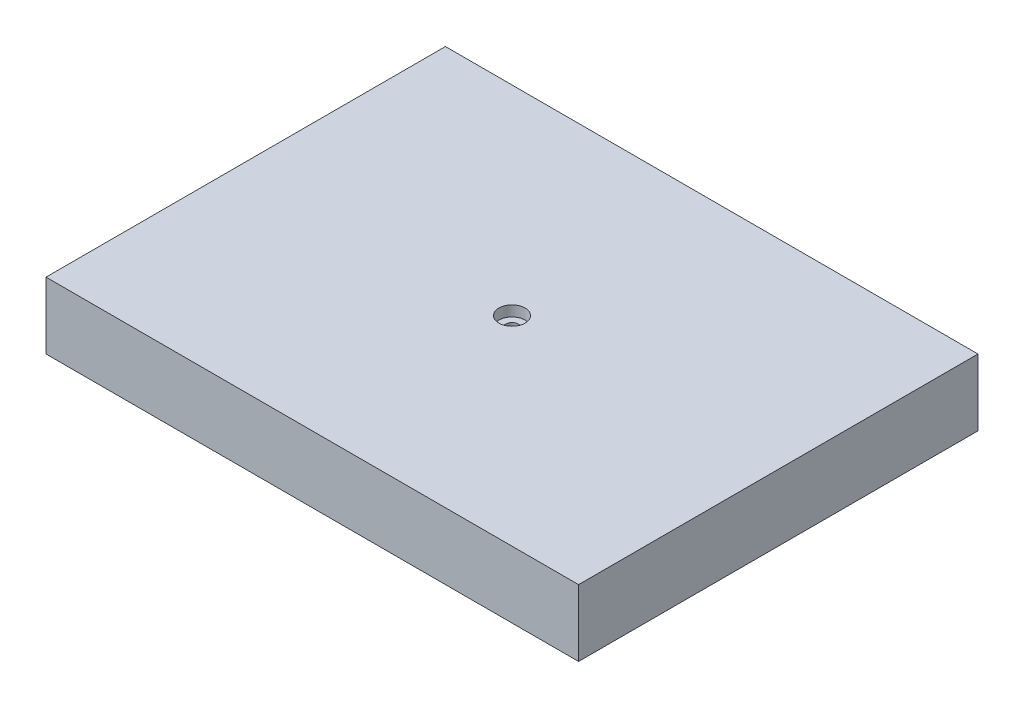
SolidWorks part; units mm, degrees
ref_plane "Front Plane" through (0, 0, 0) normal (0, 0, 1) x (1, 0, 0)
ref_plane "Top Plane" through (0, 0, 0) normal (0, 1, 0) x (1, 0, 0)
ref_plane "Right Plane" through (0, 0, 0) normal (1, 0, 0) x (0, 0, -1)
sketch "Sketch1" plane through (0, 0, 0) normal (0, 1, 0) x (1, 0, 0)
  line L1 (-50.8, 38.1) -> (50.8, 38.1)
  line L2 (-50.8, 38.1) -> (-50.8, -38.1)
  line L3 (-50.8, -38.1) -> (50.8, -38.1)
  line L4 (50.8, 38.1) -> (50.8, -38.1)
  line L5 (-50.8, 38.1) -> (50.8, -38.1) construction
  line L6 (-50.8, -38.1) -> (50.8, 38.1) construction
  point P0 (0, 0)
  dimension "D1" = 101.6
  dimension "D2" = 76.2
extrude "Boss-Extrude1" add sketch "Sketch1" along normal blind 12.7
ref_plane "Plane1" through (0, 12.7, 0) normal (0, 1, 0) x (1, 0, 0)
sketch "Sketch2" plane through (0, 12.7, 0) normal (0, 1, 0) x (1, 0, 0)
  circle A0 centre (0, 0) radius 2.5
  point P0 (0, 0)
  dimension "D1" = 5
extrude "Cut-Extrude1" cut sketch "Sketch2" against normal blind 2
sketch "Sketch5" plane through (0, 0, 0) normal (0, 1, 0) x (1, 0, 0)
  point P0 (0, 0)
hole_wizard "CBORE for M2 Hex Head Machine Screw1" positions "Sketch6" profile "Sketch8" counterbore size "M2" standard "ANSI Metric" end condition up to next
sketch "Sketch6" plane through (0, 0, 0) normal (0, -1, 0) x (-1, 0, 0)
  point P0 (0, 0)
sketch "Sketch8" plane through (0, 0, 0) normal (1, 0, 0) x (0, 0, -1)
  line L0 (0, 0) -> (0, 10.7)
  line L1 (0, 10.7) -> (1.2, 10.7)
  line L3 (1.2, 10.7) -> (1.2, 1.6)
  line L4 (1.2, 1.6) -> (3.19, 1.6)
  line L5 (3.19, 1.6) -> (3.19, 0)
  line L7 (3.19, 0) -> (0, 0)
  line L11 (0, -6.35) -> (0, 107.95) construction
  dimension "Thru Hole Dia." = 2.4
  dimension "Thru Hole Depth" = 10.7
  dimension "C'Bore Dia." = 6.38
  dimension "C'Bore Depth" = 1.6
